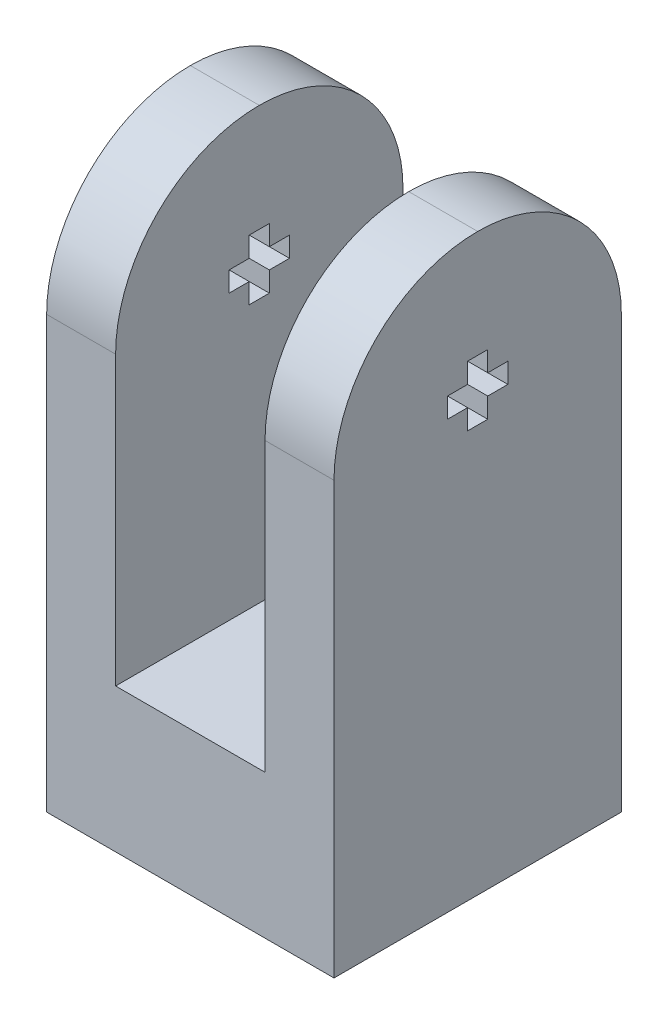
SolidWorks part; units mm, degrees
ref_plane "Front Plane" through (0, 0, 0) normal (0, 0, 1) x (1, 0, 0)
ref_plane "Top Plane" through (0, 0, 0) normal (0, 1, 0) x (1, 0, 0)
ref_plane "Right Plane" through (0, 0, 0) normal (1, 0, 0) x (0, 0, -1)
sketch "Sketch1" plane through (0, 0, 0) normal (0, 1, 0) x (1, 0, 0)
  line L1 (-12.7, -12.7) -> (12.7, -12.7)
  line L2 (-12.7, -12.7) -> (-12.7, 12.7)
  line L3 (-12.7, 12.7) -> (12.7, 12.7)
  line L4 (12.7, -12.7) -> (12.7, 12.7)
  line L5 (-12.7, -12.7) -> (12.7, 12.7) construction
  line L6 (-12.7, 12.7) -> (12.7, -12.7) construction
  point P0 (0, 0)
  dimension "D1" = 25.4
  dimension "D2" = 25.4
extrude "Boss-Extrude1" add sketch "Sketch1" along normal blind 50.8
sketch "Sketch2" plane through (0, 50.8, 0) normal (0, 1, 0) x (1, 0, 0)
  line L0 (12.7, 12.7) -> (-12.7, 12.7) construction
  line L1 (-6.604, -12.7) -> (6.604, -12.7)
  line L2 (-6.604, -12.7) -> (-6.604, 12.7)
  line L3 (-6.604, 12.7) -> (6.604, 12.7)
  line L4 (6.604, -12.7) -> (6.604, 12.7)
  line L5 (-6.604, -12.7) -> (6.604, 12.7) construction
  line L6 (-6.604, 12.7) -> (6.604, -12.7) construction
  point P0 (0, 0)
  dimension "D1" = 13.208
extrude "Cut-Extrude1" cut sketch "Sketch2" against normal blind 38.1
sketch "Sketch3" plane through (12.7, 0, 0) normal (1, 0, 0) x (0, 0, -1)
  line L0 (-0.889, 41.312) -> (0, 38.645) construction
  line L1 (-0.889, 41.312) -> (0.889, 41.312)
  line L2 (-0.889, 41.312) -> (-0.889, 39.534)
  line L3 (-0.889, 35.978) -> (0.889, 35.978)
  line L4 (0.889, 41.312) -> (0.889, 39.534)
  line L5 (0, 38.645) -> (0.889, 35.978) construction
  line L6 (0.889, 41.312) -> (0, 38.645) construction
  line L7 (-2.667, 39.534) -> (-0.889, 39.534)
  line L8 (-2.667, 39.534) -> (-2.667, 37.756)
  line L9 (-2.667, 37.756) -> (-0.889, 37.756)
  line L10 (2.667, 39.534) -> (2.667, 37.756)
  line L11 (0, 38.645) -> (-0.889, 35.978) construction
  line L12 (-2.667, 39.534) -> (0, 38.645) construction
  line L13 (0.889, 39.534) -> (2.667, 39.534)
  line L14 (0, 38.645) -> (2.667, 37.756) construction
  line L15 (0, 38.645) -> (2.667, 39.534) construction
  line L16 (-2.667, 37.756) -> (0, 38.645) construction
  line L17 (0, 38.645) -> (0, 50.8) construction
  line L18 (0.889, 37.756) -> (0.889, 35.978)
  line L19 (-0.889, 37.756) -> (-0.889, 35.978)
  line L20 (0.889, 37.756) -> (2.667, 37.756)
  line L21 (-12.7, 50.8) -> (12.7, 50.8) construction
  line L22 (0, 38.645) -> (12.7, 38.645) construction
  line L23 (12.7, 50.8) -> (12.7, 0) construction
  line L24 (0, 38.645) -> (-12.7, 38.645) construction
  line L25 (-12.7, 50.8) -> (-12.7, 0) construction
  point P0 (0, 38.645)
  point P5 (0, 38.645)
  dimension "D1" = 1.778
extrude "Cut-Extrude2" cut sketch "Sketch3" against normal through all
fillet "Fillet1" radius 12.7 4 edges at (9.652, 50.8, -12.7) (-9.652, 50.8, -12.7) (-9.652, 50.8, 12.7) (9.652, 50.8, 12.7)
